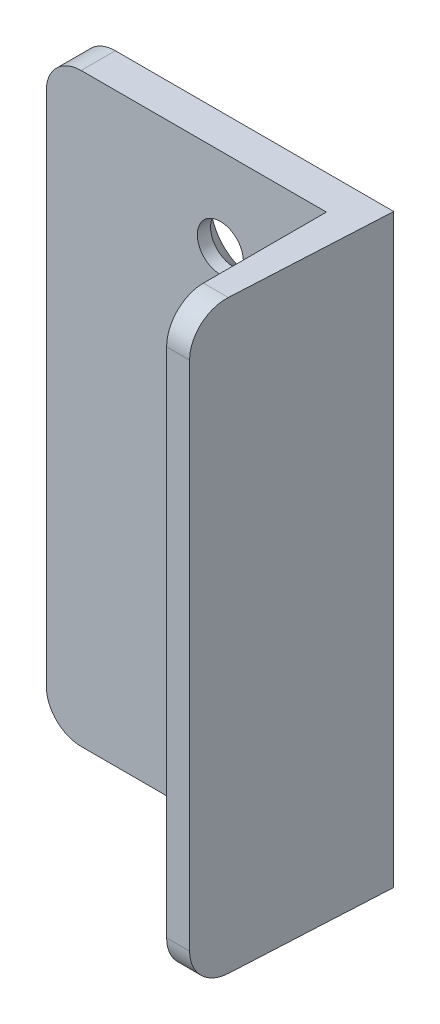
SolidWorks part; units mm, degrees
material "Free-Cutting Brass, UNS C36000"
ref_plane "Top Plane" through (0, 0, 0) normal (0, 0, 1) x (1, 0, 0)
ref_plane "Front Plane" through (0, 0, 0) normal (0, 1, 0) x (1, 0, 0)
ref_plane "Right Plane" through (0, 0, 0) normal (1, 0, 0) x (0, 0, -1)
sketch "Sketch1" plane through (0, 0, 0) normal (0, 0, 1) x (1, 0, 0)
  line L1 (-17.45, -41.95) -> (22.45, -41.95)
  line L2 (-22.45, -36.95) -> (-22.45, 36.95)
  line L3 (-17.45, 41.95) -> (22.45, 41.95)
  line L4 (22.45, -41.95) -> (22.45, 41.95)
  line L5 (-22.45, -41.95) -> (22.45, 41.95) construction
  line L6 (-22.45, 41.95) -> (22.45, -41.95) construction
  arc A0 (-22.45, -36.95) -> (-17.45, -41.95) centre (-17.45, -36.95) ccw
  arc A1 (-17.45, 41.95) -> (-22.45, 36.95) centre (-17.45, 36.95) ccw
  point P0 (0, 0)
  dimension "D3" = 5
  dimension "D1" = 44.9
  dimension "D2" = 83.9
extrude "Boss-Extrude1" add sketch "Sketch1" along normal blind 4.9
sketch "Sketch2" plane through (0, 0, 4.9) normal (0, 0, 1) x (1, 0, 0)
  line L0 (-17.45, -41.95) -> (22.45, -41.95) construction
  line L1 (22.45, 41.95) -> (17.7, 41.95)
  line L2 (22.45, 41.95) -> (22.45, -41.95)
  line L3 (22.45, -41.95) -> (17.7, -41.95)
  line L4 (17.7, 41.95) -> (17.7, -41.95)
  dimension "D1" = 4.75
extrude "Boss-Extrude2" add sketch "Sketch2" along normal blind 22.9
sketch "Sketch4" plane through (22.45, 0, 0) normal (1, 0, 0) x (0, 0, -1)
  line L16 (-27.8, 36.6718) -> (-27.8, 41.95)
  line L21 (-27.8, 41.95) -> (-22.5265, 41.95)
  line L22 (-27.8, -41.95) -> (-27.8, -36.6765)
  line L23 (-27.8, -41.95) -> (-22.5265, -41.95)
  arc A4 (-22.5265, -41.95) -> (-27.8, -36.6765) centre (-22.5265, -36.6765) cw
  arc A5 (-22.5265, 41.95) -> (-27.8, 36.6718) centre (-22.5265, 36.6765) ccw
  point P3 (-27.8, 41.95)
  point P8 (-27.8, -41.95)
  dimension "D1" = 5.2735
  dimension "D2" = 7.4578
  dimension "D3" = 7.4578
extrude "Cut-Extrude1" cut sketch "Sketch4" against normal blind 27.75
sketch "Sketch5" plane through (0, 0, 0) normal (0, 0, -1) x (-1, 0, 0)
  line L1 (-2.5, -41.95) -> (-2.5, 41.95) construction
  line L2 (17.45, -41.95) -> (-22.45, -41.95) construction
  line L3 (-22.45, 41.95) -> (17.45, 41.95) construction
  point P0 (-2.5, 29.8957)
  point P2 (-2.5, -29.8957)
  dimension "D1" = 30
  dimension "D2" = 30
hole_wizard "CSK for M6 Flat Head Machine Screw1" positions "Sketch5" profile "Sketch6" countersink size "M6" standard "ANSI Metric" end condition up to next
sketch "Sketch6" plane through (2.5, 29.8957, 0) normal (1, 0, 0) x (0, 1, 0)
  line L0 (0, 0) -> (0, 4.9)
  line L1 (0, 4.9) -> (3.3, 4.9)
  line L2 (3.3, 4.9) -> (3.3, 3)
  line L3 (3.3, 3) -> (6.3, 0)
  line L5 (6.3, 0) -> (0, 0)
  line L6 (-3.3, 3) -> (-6.3, 0) construction
  line L11 (0, -6.35) -> (0, 107.95) construction
  dimension "Thru Hole Dia." = 6.6
  dimension "Thru Hole Depth" = 4.9
  dimension "Near C'Sink Dia." = 12.6
  dimension "Near C'Sink Angle" = 90
sketch "Sketch8" plane through (22.45, 0, 0) normal (1, 0, 0) x (0, 0, -1)
  line L1 (0, -41.95) -> (-41.8347, -41.95)
  line L2 (0, -41.95) -> (0, 41.95)
  line L3 (0, 41.95) -> (-41.8347, 41.95)
  line L4 (-41.8347, -41.95) -> (-41.8347, 41.95)
  dimension "D1" = 41.8347
revolve "Cut-Revolve4" cut sketch "Sketch8" angle 3 about L2 reverse direction yes
